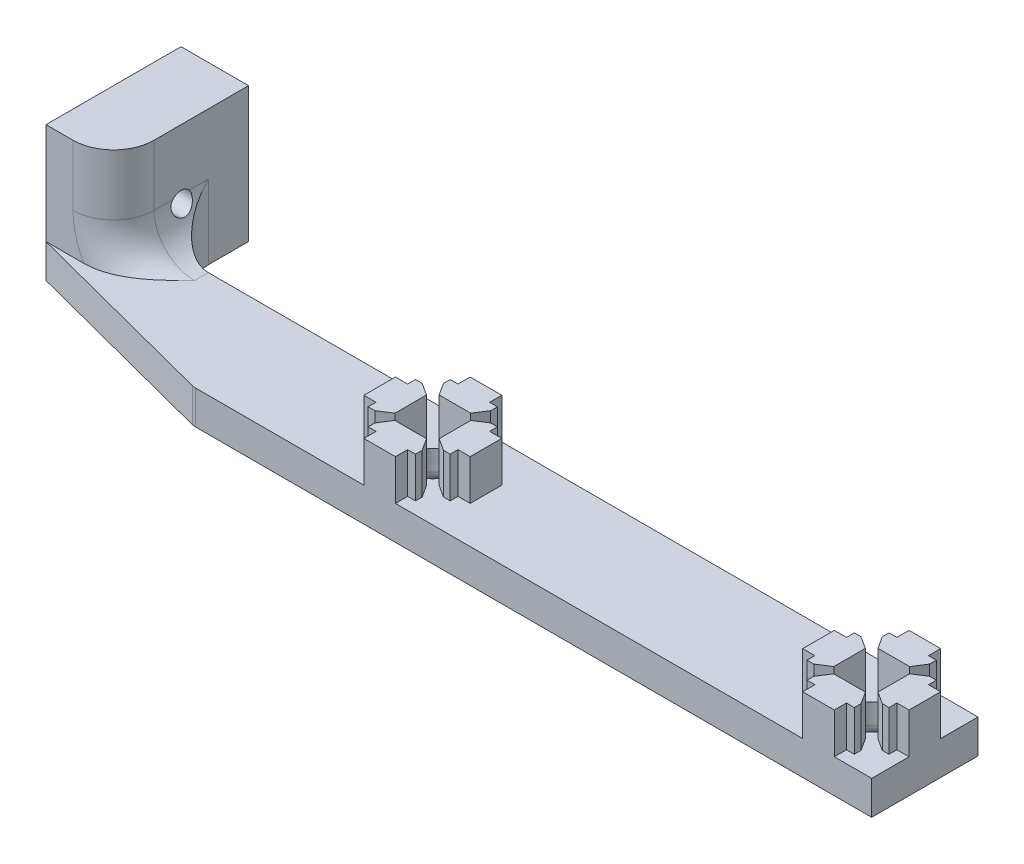
SolidWorks part; units mm, degrees
ref_plane "Front Plane" through (0, 0, 0) normal (0, 0, 1) x (1, 0, 0)
ref_plane "Top Plane" through (0, 0, 0) normal (0, 1, 0) x (1, 0, 0)
ref_plane "Right Plane" through (0, 0, 0) normal (1, 0, 0) x (0, 0, -1)
sketch "Sketch1" plane through (0, 0, 0) normal (0, 1, 0) x (1, 0, 0)
  line L0 (-2.9718, 10) -> (-2.9718, 7.714)
  line L1 (-10, 10) -> (10, 10)
  line L2 (-10, 10) -> (-10, -10)
  line L3 (-10, -10) -> (10, -10)
  line L4 (10, 10) -> (10, -10)
  line L5 (-10, 10) -> (10, -10) construction
  line L6 (-10, -10) -> (10, 10) construction
  line L7 (-2.9718, 10) -> (2.9718, 10) construction
  line L8 (-2.9718, 10) -> (-2.9718, 4.158) construction
  line L9 (-2.9718, 4.158) -> (2.9718, 4.158) construction
  line L10 (2.9718, 10) -> (2.9718, 4.158) construction
  line L11 (-4.445, 7.714) -> (4.445, 7.714) construction
  line L12 (-4.445, 7.714) -> (-4.445, 6.444) construction
  line L13 (-4.445, 6.444) -> (4.445, 6.444) construction
  line L14 (4.445, 7.714) -> (4.445, 6.444) construction
  line L15 (-4.445, 7.714) -> (4.445, 6.444) construction
  line L16 (-4.445, 6.444) -> (4.445, 7.714) construction
  line L17 (-2.9718, 7.714) -> (-4.445, 7.714)
  line L18 (-4.445, 7.714) -> (-4.445, 6.444)
  line L19 (-4.445, 6.444) -> (-2.9718, 4.158)
  line L20 (-2.9718, 4.158) -> (2.9718, 4.158)
  line L21 (2.9718, 4.158) -> (4.445, 6.444)
  line L22 (4.445, 6.444) -> (4.445, 7.714)
  line L23 (4.445, 7.714) -> (2.9718, 7.714)
  line L24 (2.9718, 7.714) -> (2.9718, 10)
  line L25 (2.9718, 10) -> (-2.9718, 10)
  line L26 (4.158, -2.9718) -> (4.158, 2.9718)
  line L27 (4.158, 2.9718) -> (6.444, 4.445)
  line L28 (6.444, 4.445) -> (7.714, 4.445)
  line L29 (7.714, 4.445) -> (7.714, 2.9718)
  line L30 (7.714, 2.9718) -> (10, 2.9718)
  line L31 (10, -2.9718) -> (10, 2.9718) construction
  line L32 (10, 2.9718) -> (10, -2.9718)
  line L33 (10, -2.9718) -> (7.714, -2.9718)
  line L34 (7.714, -2.9718) -> (7.714, -4.445)
  line L35 (7.714, -4.445) -> (6.444, -4.445)
  line L36 (6.444, -4.445) -> (4.158, -2.9718)
  line L37 (2.9718, -10) -> (-2.9718, -10) construction
  line L38 (4.445, -6.444) -> (2.9718, -4.158)
  line L39 (4.445, -7.714) -> (4.445, -6.444)
  line L40 (2.9718, -7.714) -> (4.445, -7.714)
  line L41 (2.9718, -10) -> (2.9718, -7.714)
  line L42 (-2.9718, -10) -> (2.9718, -10)
  line L43 (-2.9718, -7.714) -> (-2.9718, -10)
  line L44 (-4.445, -7.714) -> (-2.9718, -7.714)
  line L45 (-4.445, -6.444) -> (-4.445, -7.714)
  line L46 (-2.9718, -4.158) -> (-4.445, -6.444)
  line L47 (2.9718, -4.158) -> (-2.9718, -4.158)
  line L48 (-10, 2.9718) -> (-10, -2.9718) construction
  line L49 (-10, -2.9718) -> (-10, 2.9718)
  line L50 (-7.714, -2.9718) -> (-10, -2.9718)
  line L51 (-7.714, -4.445) -> (-7.714, -2.9718)
  line L52 (-6.444, -4.445) -> (-7.714, -4.445)
  line L53 (-4.158, -2.9718) -> (-6.444, -4.445)
  line L54 (-4.158, 2.9718) -> (-4.158, -2.9718)
  line L55 (-6.444, 4.445) -> (-4.158, 2.9718)
  line L56 (-7.714, 4.445) -> (-6.444, 4.445)
  line L57 (-7.714, 2.9718) -> (-7.714, 4.445)
  line L58 (-10, 2.9718) -> (-7.714, 2.9718)
  line L59 (0, 7.079) -> (0, 7.714) construction
  point P0 (0, 0)
  point P12 (0, 4.158)
  point P13 (0, 7.079)
  dimension "D3" = 10
  dimension "D1" = 20
  dimension "D2" = 20
  dimension "D4" = 5.9436
  dimension "D5" = 10
  dimension "D6" = 5.842
  dimension "D7" = 2.286
  dimension "D8" = 3.556
  dimension "D9" = 8.89
extrude "Boss-Extrude1" add sketch "Sketch1" along normal blind 7.62 contours L23 L24 L1 L0 L17 L18 L19 L20 L21 L22 | L26 L27 L28 L29 L30 L32 L33 L34 L35 L36 | L49 L58 L57 L56 L55 L54 L53 L52 L51 L50 | L38 L47 L46 L45 L44 L43 L42 L41 L40 L39 region at (0, 0, -6.9665)
sketch "Sketch2" plane through (0, 0, 0) normal (0, -1, 0) x (1, 0, 0)
  line L1 (10, -10) -> (-155.1, -10)
  line L2 (10, -10) -> (10, 10)
  line L3 (10, 10) -> (-155.1, 10)
  line L4 (-155.1, -10) -> (-155.1, 10)
  line L5 (10, -10) -> (-155.1, 10) construction
  line L6 (10, 10) -> (-155.1, -10) construction
  line L7 (-2.9718, -10) -> (2.9718, -10) construction
  line L8 (10, -2.9718) -> (10, 2.9718) construction
  dimension "D1" = 165.1
  dimension "D2" = 20
  dimension "D3" = 0
  dimension "D4" = 0
extrude "Boss-Extrude2" add sketch "Sketch2" along normal blind 6.35
pattern_linear "LPattern2" count 2 spacing 82.55 along (-1, 0, 0) of "Boss-Extrude1"
sketch "Sketch4" plane through (0, -6.35, 0) normal (0, -1, 0) x (-1, 0, 0)
  line L0 (155.1, 10) -> (155.1, -0.2108) construction
  line L1 (155.1, -10) -> (155.1, 10) construction
  line L2 (155.1, -10) -> (117.5588, -10)
  line L3 (-10, -10) -> (155.1, -10) construction
  line L4 (117.5588, -10) -> (155.1, -0.2108)
  line L5 (155.1, -0.2108) -> (155.1, -10)
  dimension "D1" = 10.2108
  dimension "D2" = 37.5412
extrude "Cut-Extrude1" cut sketch "Sketch4" against normal through all
fillet "Fillet1" radius 2.54 1 edges at (-117.5588, -3.175, 10)
sketch "Sketch6" plane through (-155.1, 0, 0) normal (-1, 0, 0) x (0, 0, 1)
  line L1 (0.2108, -6.35) -> (-25.1892, -6.35)
  line L2 (0.2108, -6.35) -> (0.2108, 19.05)
  line L3 (0.2108, 19.05) -> (-25.1892, 19.05)
  line L4 (-25.1892, -6.35) -> (-25.1892, 19.05)
  dimension "D1" = 25.4
  dimension "D2" = 25.4
extrude "Boss-Extrude7" add sketch "Sketch6" against normal blind 12.7
fillet "Fillet3" radius 7.62 2 edges at (-142.4, 0, -4.8946) (-142.4, -3.175, -10)
fillet "Fillet5" radius 7.62 2 edges at (-140.1682, 2.2318, 0.2108) (-142.4, 13.335, 0.2108)
sketch "Sketch11" plane through (-155.1, 0, 0) normal (-1, 0, 0) x (0, 0, 1)
  line L0 (-25.1892, -6.35) -> (0.2108, 19.05) construction
  circle A0 centre (-12.4892, 6.35) radius 1.9844
  dimension "D1" = 3.9688
extrude "Cut-Extrude3" cut sketch "Sketch11" against normal through all
sketch "Sketch13" plane through (0, 0, 0) normal (0, 1, 0) x (1, 0, 0)
  line L0 (-86.708, -2.9718) -> (-88.994, -4.445) construction
  line L1 (4.158, 2.9718) -> (-4.158, 2.9718) construction
  line L2 (4.158, 2.9718) -> (4.158, -2.9718) construction
  line L3 (4.158, -2.9718) -> (-4.158, -2.9718) construction
  line L4 (-4.158, 2.9718) -> (-4.158, -2.9718) construction
  line L5 (-78.392, 2.9718) -> (-86.708, 2.9718) construction
  line L6 (-78.392, 2.9718) -> (-78.392, -2.9718) construction
  line L7 (-78.392, -2.9718) -> (-86.708, -2.9718) construction
  line L8 (-86.708, 2.9718) -> (-86.708, -2.9718) construction
  line L9 (-86.708, 2.9718) -> (-86.708, -2.9718) construction
  line L10 (-82.55, 2.9718) -> (-82.55, -2.9718) construction
  circle A0 centre (0, 0) radius 3.5
  circle A1 centre (-82.55, 0) radius 3.5
  dimension "D1" = 7
  dimension "D2" = 7
extrude "Cut-Extrude5" cut sketch "Sketch13" against normal through all
fillet "Fillet6" radius 2.54 2 edges at (0, -6.35, 3.5) (-82.55, -6.35, 3.5)
